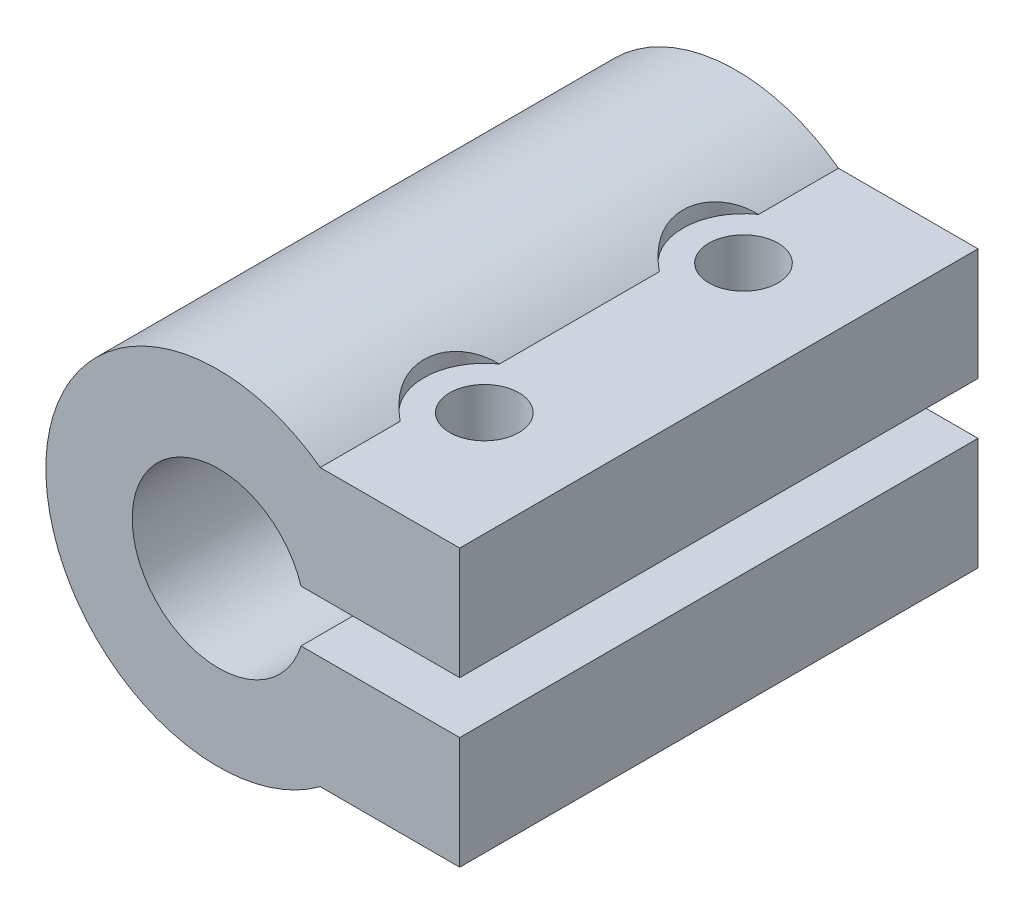
SolidWorks part; units mm, degrees
material "ABS"
ref_plane "Front Plane" through (0, 0, 0) normal (0, 0, 1) x (1, 0, 0)
ref_plane "Top Plane" through (0, 0, 0) normal (0, 1, 0) x (1, 0, 0)
ref_plane "Right Plane" through (0, 0, 0) normal (1, 0, 0) x (0, 0, -1)
sketch "Sketch1" plane through (0, 0, 0) normal (1, 0, 0) x (0, 0, -1)
  line L1 (-14.0722, 8.7371) -> (15.9278, 8.7371)
  line L2 (-14.0722, 8.7371) -> (-14.0722, -7.2629)
  line L3 (-14.0722, -7.2629) -> (15.9278, -7.2629)
  line L4 (15.9278, 8.7371) -> (15.9278, -7.2629)
  dimension "D1" = 30
  dimension "D2" = 16
extrude "Boss-Extrude1" add sketch "Sketch1" against normal blind 14
sketch "Sketch3" plane through (0, 0, -15.9278) normal (0, 0, -1) x (-1, 0, 0)
  line L0 (14, -7.2629) -> (14, 8.7371) construction
  circle A0 centre (14, 0.7371) radius 9.955
  dimension "D1" = 19.91
extrude "Boss-Extrude2" add sketch "Sketch3" against normal blind 30
sketch "Sketch4" plane through (0, 0, -15.9278) normal (0, 0, -1) x (-1, 0, 0)
  line L1 (0, -7.2629) -> (0, 8.7371) construction
  line L2 (0, -0.7629) -> (11.4, -0.7629)
  line L3 (0, -0.7629) -> (0, 2.2371)
  line L4 (0, 2.2371) -> (11.4, 2.2371)
  line L5 (11.4, -0.7629) -> (11.4, 2.2371)
  line L6 (0, -0.7629) -> (11.4, 2.2371) construction
  line L7 (0, 2.2371) -> (11.4, -0.7629) construction
  line L9 (8.0753, -7.2629) -> (0, -7.2629) construction
  point P0 (5.7, 0.7371)
  dimension "D1" = 11.4
  dimension "D2" = 0
  dimension "D3" = 3
  dimension "D4" = 8
extrude "Cut-Extrude1" cut sketch "Sketch4" against normal blind 30
sketch "Sketch5" plane through (0, 0, 14.0722) normal (0, 0, 1) x (1, 0, 0)
  line L4 (0, -0.7629) -> (-11.4, -0.7629) construction
  circle A0 centre (-13.955, 0.7371) radius 5
  arc A1 (-8.0753, 8.7371) -> (-8.0753, -7.2629) centre (-14, 0.7371) ccw construction
  point P2 (-23.955, 0.7371)
  dimension "D1" = 10
  dimension "D2" = 10
  dimension "D3" = 1.5
extrude "Cut-Extrude2" cut sketch "Sketch5" against normal blind 15
sketch "Sketch6" plane through (0, 0, -15.9278) normal (0, 0, -1) x (-1, 0, 0)
  line L0 (16, 2.9871) -> (16, -1.5129)
  line L3 (8.0753, -7.2629) -> (0, -7.2629) construction
  arc A0 (16, 2.9871) -> (16, -1.5129) centre (14.0157, 0.7371) ccw
  arc A1 (8.0753, -7.2629) -> (8.0753, 8.7371) centre (14, 0.7371) ccw construction
  dimension "D1" = 16
  dimension "D3" = 3
  dimension "D2" = 4.5
  dimension "D4" = 8
extrude "Cut-Extrude5" cut sketch "Sketch6" against normal blind 15
sketch "Sketch7" plane through (0, -7.2629, 0) normal (0, -1, 0) x (1, 0, 0)
  line L0 (-8.0753, -15.9278) -> (0, -15.9278) construction
  line L1 (-6.0741, 3.2222) -> (-3.1729, 4.8972)
  line L2 (-3.1729, 4.8972) -> (-3.1729, 8.2472)
  line L3 (-3.1729, 8.2472) -> (-6.0741, 9.9222)
  line L4 (-6.0741, 9.9222) -> (-8.9753, 8.2472)
  line L5 (-8.9753, 8.2472) -> (-8.9753, 4.8972)
  line L6 (-8.9753, 4.8972) -> (-6.0741, 3.2222)
  line L7 (-6.0741, -11.7778) -> (-3.1729, -10.1028)
  line L8 (-3.1729, -10.1028) -> (-3.1729, -6.7528)
  line L9 (-3.1729, -6.7528) -> (-6.0741, -5.0778)
  line L10 (-6.0741, -5.0778) -> (-8.9753, -6.7528)
  line L11 (-8.9753, -6.7528) -> (-8.9753, -10.1028)
  line L12 (-8.9753, -10.1028) -> (-6.0741, -11.7778)
  line L13 (-8.0753, 14.0722) -> (0, 14.0722) construction
  line L14 (-8.9753, -1.4278) -> (-1.5, -1.4278)
  line L16 (-8.9753, -1.4278) -> (-8.9753, -0.4278)
  line L17 (-8.9753, -0.4278) -> (-1.5, -0.4278)
  line L18 (-1.5, -1.4278) -> (-1.5, -0.4278)
  line L19 (-8.9753, -1.4278) -> (-1.5, -0.4278) construction
  line L20 (-8.9753, -0.4278) -> (-1.5, -1.4278) construction
  line L22 (-8.0753, 14.0722) -> (-8.0753, -15.9278) construction
  line L23 (0, -15.9278) -> (0, 14.0722) construction
  circle A0 centre (-6.0741, 6.5722) radius 2.9012 construction
  circle A1 centre (-6.0741, -8.4278) radius 2.9012 construction
  circle A2 centre (-6.0741, -8.4278) radius 2
  circle A3 centre (-6.0741, 6.5722) radius 2
  point P18 (-5.2377, -0.9278)
  line M10 (-8.0753, 14.0722) -> (-8.0753, -15.9278)
  dimension "D11" = 4
  dimension "D12" = 4
  dimension "D1" = 1
  dimension "D2" = 6.7
  dimension "D3" = 3.65
  dimension "D4" = 4.15
  dimension "D5" = 3.65
  dimension "D6" = 4.15
  dimension "D7" = 0.9
  dimension "D8" = 0.9
  dimension "D9" = 0.9
  dimension "D10" = 1.5
extrude "Cut-Extrude7" cut sketch "Sketch7" against normal blind 3 and the other way blind 1 contours L6 L1 L2 L3 L4 A3 M10 | L5 L6 L4 M10 | L14 L18 L17 M10 | L12 L7 L8 L9 L10 A2 M10 | L16 L17 L18 L14 | L11 L12 L7 L8 L9 L10 region at (-7.0332, -7.2629, 3.8718) region at (-7.0332, -7.2629, -5.7274) region at (-4.7877, -7.2629, -0.9278) region at (-8.5052, -7.2629, 6.5722)
extrude "Cut-Extrude9" cut sketch "Sketch7<4>" against normal through all contours A2 | A3 region at (-6.0741, -7.2629, -8.4278) region at (-6.0741, -7.2629, 6.5722)
sketch "Sketch7<4>" plane through (0, -7.2629, 0) normal (0, -1, 0) x (1, 0, 0) same geometry as "Sketch7"
sketch "Sketch11" plane through (0, 8.7371, 0) normal (0, 1, 0) x (1, 0, 0)
  circle A0 centre (-6.0741, -6.5722) radius 3.5
  circle A2 centre (-6.0741, 8.4278) radius 3.5
  dimension "D1" = 7
  dimension "D2" = 7
extrude "Cut-Extrude10" cut sketch "Sketch11" along normal blind 0.93
